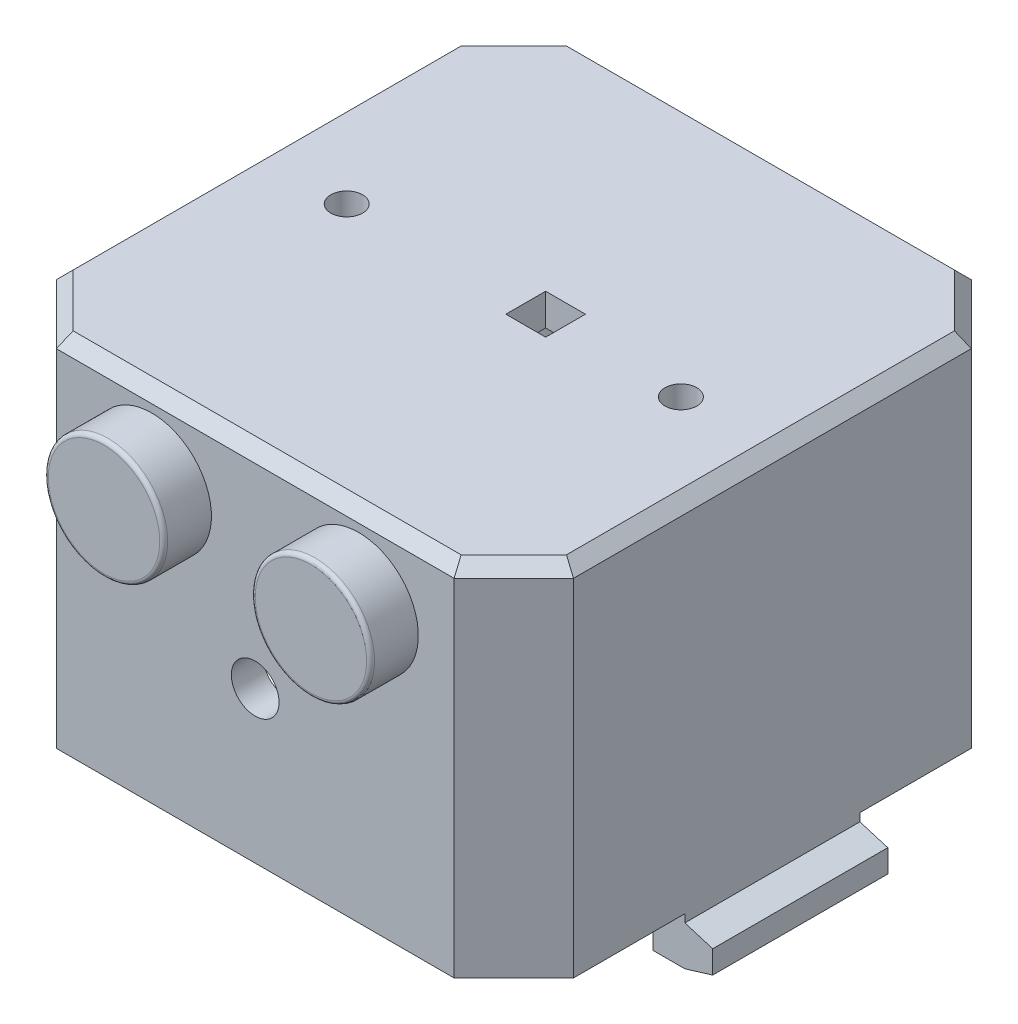
SolidWorks part; units mm, degrees
ref_plane "Alzado" through (0, 0, 0) normal (0, 0, 1) x (1, 0, 0)
ref_plane "Planta" through (0, 0, 0) normal (0, 1, 0) x (1, 0, 0)
ref_plane "Vista lateral" through (0, 0, 0) normal (1, 0, 0) x (0, 0, -1)
sketch "Croquis1" plane through (0, 0, 0) normal (0, 1, 0) x (1, 0, 0)
  line L1 (-25, -32.5) -> (25, -32.5)
  line L3 (-25, 32.5) -> (25, 32.5)
  line L5 (-25, -32.5) -> (25, 32.5) construction
  line L6 (-25, 32.5) -> (25, -32.5) construction
  line L10 (32.5, 25) -> (32.5, -25)
  line L11 (25, -32.5) -> (32.5, -25)
  line L12 (32.5, 25) -> (25, 32.5)
  line L13 (-32.5, 25) -> (-32.5, -25)
  line L14 (-32.5, -25) -> (-25, -32.5)
  line L15 (-32.5, 25) -> (-25, 32.5)
  point P0 (0, 0)
  point P10 (0, 32.5)
  dimension "D1" = 65
  dimension "D2" = 65
  dimension "D3" = 50
  dimension "D4" = 50
  dimension "D5" = 25
  dimension "D6" = 25
extrude "Saliente-Extruir1" add sketch "Croquis1" along normal blind 45
shell "Vaciado2" thickness 4 removed face at (0, 0, 0)
chamfer "Chaflán3" distance 1.5 angle 45 8 edges at (0, 45, -32.5) (32.5, 45, 0) (0, 45, 32.5) (-32.5, 45, 0) (-28.75, 45, 28.75) (28.75, 45, 28.75) (28.75, 45, -28.75) (-28.75, 45, -28.75)
sketch "Croquis2" plane through (0, 0, 32.5) normal (0, 0, 1) x (1, 0, 0)
  line L0 (0, 0) -> (0, 6.916) construction
  circle A0 centre (13, 35) radius 7.5
  circle A1 centre (-13, 35) radius 7.5
  dimension "D1" = 15
  dimension "D2" = 13
  dimension "D3" = 35
extrude "Saliente-Extruir2" add sketch "Croquis2" along normal blind 6
sketch "Croquis4" plane through (0, 0, 28.5) normal (0, 0, -1) x (-1, 0, 0)
  line L0 (0, 0) -> (0, 4.7403) construction
  line L1 (0, 0) -> (0, 6.916) construction
  circle A0 centre (-13, 35) radius 5
  circle A1 centre (13, 35) radius 5
  dimension "D1" = 10
extrude "Cortar-Extruir2" cut sketch "Croquis4" against normal blind 8
fillet "Redondeo1" radius 0.5 2 edges at (-20.5, 35, 38.5) (20.5, 35, 38.5)
sketch "Croquis5" plane through (0, 0, 32.5) normal (0, 0, 1) x (1, 0, 0)
  circle A0 centre (0, 19) radius 3
  dimension "D2" = 6
  dimension "D1" = 19
extrude "Cortar-Extruir3" cut sketch "Croquis5" against normal blind 10
sketch "Croquis13" plane through (0, 0, 36.5) normal (0, 0, -1) x (-1, 0, 0)
  circle A0 centre (-13, 35) radius 2.6
  circle A1 centre (13, 35) radius 2.6
  circle A2 centre (13, 35) radius 5
  circle A3 centre (-13, 35) radius 5
  dimension "D1" = 5.2
  dimension "D2" = 5.2
extrude "Saliente-Extruir8" add sketch "Croquis13" along normal blind 8
sketch "Croquis7" plane through (0, 0, 28.5) normal (0, 0, -1) x (-1, 0, 0)
  line L0 (23.3431, 0) -> (-23.3431, 0) construction
  line L1 (-14.08, 8) -> (-9.08, 8)
  line L2 (-14.08, 8) -> (-14.08, 13)
  line L3 (-14.08, 13) -> (-9.08, 13)
  line L4 (-9.08, 8) -> (-9.08, 13)
  line L5 (-14.08, 8) -> (-9.08, 13) construction
  line L6 (-14.08, 13) -> (-9.08, 8) construction
  line L8 (-14.08, 25.5) -> (-9.08, 25.5)
  line L9 (-14.08, 25.5) -> (-14.08, 30.5)
  line L10 (-14.08, 30.5) -> (-9.08, 30.5)
  line L11 (-9.08, 25.5) -> (-9.08, 30.5)
  line L12 (-14.08, 25.5) -> (-9.08, 30.5) construction
  line L13 (-14.08, 30.5) -> (-9.08, 25.5) construction
  line L14 (13.93, 13) -> (8.93, 8) construction
  line L15 (13.93, 8) -> (8.93, 13) construction
  line L16 (8.93, 8) -> (8.93, 13)
  line L17 (13.93, 13) -> (8.93, 13)
  line L18 (13.93, 8) -> (13.93, 13)
  line L19 (13.93, 8) -> (8.93, 8)
  line L20 (13.93, 30.5) -> (8.93, 25.5) construction
  line L21 (13.93, 25.5) -> (8.93, 30.5) construction
  line L22 (8.93, 25.5) -> (8.93, 30.5)
  line L23 (13.93, 30.5) -> (8.93, 30.5)
  line L24 (13.93, 25.5) -> (13.93, 30.5)
  line L25 (13.93, 25.5) -> (8.93, 25.5)
  point P0 (-11.58, 10.5)
  point P8 (-11.58, 28)
  point P13 (0, 0)
  point P15 (11.43, 10.5)
  point P16 (11.43, 28)
  point P20 (11.43, 10.5)
  point P25 (11.43, 28)
  point P26 (-11.58, 28)
  point P27 (11.43, 28)
  point P28 (11.43, 10.5)
  point P29 (-11.58, 10.5)
  dimension "D1" = 10.5
  dimension "D2" = 5
  dimension "D3" = 5
  dimension "D4" = 11.58
  dimension "D5" = 5
  dimension "D6" = 5
  dimension "D7" = 28
  dimension "D8" = 23.01
  dimension "D9" = 23.01
  dimension "D10" = 5
  dimension "D11" = 5
  dimension "D12" = 5
  dimension "D13" = 5
  dimension "D14" = 10.5
  dimension "D15" = 28
extrude "Saliente-Extruir3" add sketch "Croquis7" along normal blind 1
sketch "Croquis8" plane through (0, 0, 27.5) normal (0, 0, -1) x (-1, 0, 0)
  line L0 (0, 0) -> (0, 4.8013) construction
  line L1 (23.3431, 0) -> (-23.3431, 0) construction
  circle A0 centre (-11.505, 10.4893) radius 2.5
  circle A1 centre (-11.505, 27.9763) radius 2.5
  circle A2 centre (11.505, 10.4893) radius 2.5
  circle A3 centre (11.505, 27.9763) radius 2.5
  dimension "D1" = 5
  dimension "D2" = 5
  dimension "D5" = 5
  dimension "D3" = 23.01
  dimension "D4" = 23.01
extrude "Saliente-Extruir4" add sketch "Croquis8" along normal blind 1
sketch "Croquis9" plane through (0, 0, 26.5) normal (0, 0, -1) x (-1, 0, 0)
  circle A0 centre (-11.505, 27.9763) radius 1.6
  circle A1 centre (-11.505, 10.4893) radius 1.6
  circle A2 centre (11.505, 10.4893) radius 1.6
  circle A3 centre (11.505, 27.9763) radius 1.6
  dimension "D1" = 3.2
  dimension "D2" = 3.2
  dimension "D3" = 3.2
  dimension "D4" = 3.2
extrude "Cortar-Extruir5" cut sketch "Croquis9" against normal blind 4
sketch "Croquis12" plane through (0, 41, 0) normal (0, -1, 0) x (1, 0, 0)
  line L0 (0, 0) -> (-5.199, 0) construction
  line L1 (-21.9, -8.93) -> (21.9, -8.93) construction
  line L2 (-21.9, -8.93) -> (-21.9, 8.93) construction
  line L3 (-21.9, 8.93) -> (21.9, 8.93) construction
  line L4 (21.9, -8.93) -> (21.9, 8.93) construction
  line L5 (-21.9, -8.93) -> (21.9, 8.93) construction
  line L6 (-21.9, 8.93) -> (21.9, -8.93) construction
  line L7 (0, 0) -> (0, 4.1573) construction
  circle A0 centre (-20.65, 7.68) radius 0.8
  circle A1 centre (-20.65, 7.68) radius 1.15
  circle A2 centre (-20.65, -7.68) radius 1.15
  circle A3 centre (-20.65, -7.68) radius 0.8
  circle A4 centre (20.65, 7.68) radius 1.15
  circle A5 centre (20.65, 7.68) radius 0.8
  circle A6 centre (20.65, -7.68) radius 1.15
  circle A7 centre (20.65, -7.68) radius 0.8
  point P0 (0, 0)
  dimension "D6" = 1.6
  dimension "D4" = 2.3
  dimension "D1" = 43.8
  dimension "D2" = 17.86
  dimension "D3" = 1.25
  dimension "D7" = 1.25
extrude "Saliente-Extruir7" add sketch "Croquis12" along normal blind 6
sketch "Croquis14" plane through (0, 41, 0) normal (0, -1, 0) x (1, 0, 0)
  line L1 (-22.15, 6.43) -> (-19.15, 6.43)
  line L2 (-22.15, 6.43) -> (-22.15, 8.93)
  line L3 (-22.15, 8.93) -> (-19.15, 8.93)
  line L4 (-19.15, 6.43) -> (-19.15, 8.93)
  line L5 (-22.15, 6.43) -> (-19.15, 8.93) construction
  line L6 (-22.15, 8.93) -> (-19.15, 6.43) construction
  line L7 (-22.15, -8.93) -> (-19.15, -8.93)
  line L8 (-22.15, -8.93) -> (-22.15, -6.43)
  line L9 (-22.15, -6.43) -> (-19.15, -6.43)
  line L10 (-19.15, -8.93) -> (-19.15, -6.43)
  line L11 (-22.15, -8.93) -> (-19.15, -6.43) construction
  line L12 (-22.15, -6.43) -> (-19.15, -8.93) construction
  line L13 (19.15, 6.43) -> (22.15, 6.43)
  line L14 (19.15, 6.43) -> (19.15, 8.93)
  line L15 (19.15, 8.93) -> (22.15, 8.93)
  line L16 (22.15, 6.43) -> (22.15, 8.93)
  line L17 (19.15, 6.43) -> (22.15, 8.93) construction
  line L18 (19.15, 8.93) -> (22.15, 6.43) construction
  line L19 (19.15, -8.93) -> (22.15, -8.93)
  line L20 (19.15, -8.93) -> (19.15, -6.43)
  line L21 (19.15, -6.43) -> (22.15, -6.43)
  line L22 (22.15, -8.93) -> (22.15, -6.43)
  line L23 (19.15, -8.93) -> (22.15, -6.43) construction
  line L24 (19.15, -6.43) -> (22.15, -8.93) construction
  point P0 (-20.65, 7.68)
  point P6 (-20.65, -7.68)
  point P12 (20.65, 7.68)
  point P18 (20.65, -7.68)
  dimension "D1" = 3
  dimension "D2" = 2.5
  dimension "D3" = 3
  dimension "D4" = 2.5
  dimension "D5" = 3
  dimension "D6" = 2.5
  dimension "D7" = 3
  dimension "D8" = 2.5
extrude "Saliente-Extruir9" add sketch "Croquis14" along normal blind 5
sketch "Croquis15" plane through (-32.5, 0, 0) normal (-1, 0, 0) x (0, 0, 1)
  line L1 (-6, 40.5) -> (6, 40.5)
  line L2 (-6, 40.5) -> (-6, 32.5)
  line L3 (-6, 32.5) -> (6, 32.5)
  line L4 (6, 40.5) -> (6, 32.5)
  dimension "D1" = 8
  dimension "D2" = 12
  dimension "D3" = 3
  dimension "D4" = 19
extrude "Cortar-Extruir6" cut sketch "Croquis15" against normal blind 7
sketch "Croquis16" plane through (0, 0, -28.5) normal (0, 0, 1) x (1, 0, 0)
  line L2 (18.95, 6.05) -> (6.55, 6.05)
  line L3 (18.95, 6.05) -> (18.95, 18.45)
  line L4 (18.95, 18.45) -> (6.55, 18.45)
  line L5 (6.55, 6.05) -> (6.55, 18.45)
  line L6 (5.5, 5) -> (20, 5)
  line L7 (5.5, 5) -> (5.5, 19.5)
  line L8 (5.5, 19.5) -> (20, 19.5)
  line L9 (20, 5) -> (20, 19.5)
  line L10 (5.5, 5) -> (20, 19.5) construction
  line L11 (5.5, 19.5) -> (20, 5) construction
  line L12 (18.95, 6.05) -> (6.55, 18.45) construction
  line L13 (18.95, 18.45) -> (6.55, 6.05) construction
  point P0 (12.75, 12.25)
  point P4 (12.75, 12.25)
  dimension "D1" = 12.4
  dimension "D2" = 12.4
  dimension "D3" = 5
  dimension "D4" = 5
  dimension "D5" = 14.5
  dimension "D6" = 14.5
extrude "Saliente-Extruir10" add sketch "Croquis16" along normal blind 3
sketch "Croquis17" plane through (0, 0, -28.5) normal (0, 0, 1) x (1, 0, 0)
  circle A0 centre (12.75, 12.25) radius 5.5
  point P4 (12.75, 12.25)
  dimension "D1" = 11
extrude "Cortar-Extruir7" cut sketch "Croquis17" against normal through all
sketch "Croquis18" plane through (0, 0, 0) normal (0, -1, 0) x (1, 0, 0)
  line L1 (-32.5, 11) -> (-28.5, 11)
  line L2 (-32.5, 11) -> (-32.5, -11)
  line L3 (-32.5, -11) -> (-28.5, -11)
  line L4 (-28.5, 11) -> (-28.5, -11)
  line L5 (-32.5, -25) -> (-32.5, 25) construction
  line L6 (0, 0) -> (0, 8.739) construction
  line L7 (28.5, 11) -> (28.5, -11)
  line L8 (32.5, -11) -> (28.5, -11)
  line L9 (32.5, 11) -> (32.5, -11)
  line L10 (32.5, 11) -> (28.5, 11)
  point P4 (-28.5, 0)
  dimension "D1" = 4
  dimension "D2" = 22
extrude "Saliente-Extruir11" add sketch "Croquis18" along normal blind 6
sketch "Croquis19" plane through (0, 0, 11) normal (0, 0, 1) x (1, 0, 0)
  line L0 (-32.5, -3.5) -> (-34.5, -3.5) construction
  line L1 (36, -2.0667) -> (36, -4.9333)
  line L2 (-34.5, -2.0568) -> (-32.5, -1)
  line L3 (-32.5, -6) -> (-32.5, 0)
  line L4 (-32.5, -6) -> (-32.5, -1)
  line L5 (-32.5, -6) -> (-34.5, -4.9432)
  line L6 (0, 0) -> (0, 6.3616) construction
  line L7 (-25, 0) -> (25, 0) construction
  line L8 (32.5, -3.5) -> (36, -3.5) construction
  line L9 (32.5, -6) -> (36, -4.9333)
  line L10 (32.5, -6) -> (32.5, -1)
  line L11 (32.5, -6) -> (32.5, 0)
  line L12 (36, -2.0667) -> (32.5, -1)
  line L14 (-34.5, -2.0568) -> (-34.5, -4.9432)
  line M6 (-32.5, 0) -> (-32.5, -6)
  dimension "D1" = 2
  dimension "D2" = 3.5
extrude "Saliente-Extruir13" add sketch "Croquis19" against normal blind 22 contours L5 L2 M6 | L12 L10 L9 region at (34.0918, -3.5, 11) region at (-33.4107, -3.5, 11)
sketch "Croquis20" plane through (0, 45, 0) normal (0, 1, 0) x (1, 0, 0)
  line L1 (6.0029, -2) -> (1.0029, -2)
  line L2 (6.0029, -2) -> (6.0029, 3)
  line L3 (6.0029, 3) -> (1.0029, 3)
  line L4 (1.0029, -2) -> (1.0029, 3)
  dimension "D1" = 5
  dimension "D2" = 5
  dimension "D3" = 2
extrude "Cortar-Extruir8" cut sketch "Croquis20" against normal blind 10
sketch "Croquis10" plane through (0, 45, 0) normal (0, 1, 0) x (1, 0, 0)
  line L0 (-31, 24.3787) -> (-31, -24.3787) construction
  line L1 (-31, -4) -> (-11, -4) construction
  line L2 (-31, -4) -> (-31, 4) construction
  line L3 (-31, 4) -> (-11, 4) construction
  line L4 (-11, -4) -> (-11, 4) construction
  line L5 (-31, -4) -> (-11, 4) construction
  line L6 (-31, 4) -> (-11, -4) construction
  line L7 (0, 0) -> (0, 7.307) construction
  line L8 (31, 4) -> (11, -4) construction
  line L9 (31, -4) -> (11, 4) construction
  line L10 (11, -4) -> (11, 4) construction
  line L11 (31, 4) -> (11, 4) construction
  line L12 (31, -4) -> (31, 4) construction
  line L13 (31, -4) -> (11, -4) construction
  circle A0 centre (-21, 0) radius 2
  circle A1 centre (21, 0) radius 2
  point P0 (-21, 0)
  point P14 (21, 0)
  dimension "D3" = 4
  dimension "D4" = 4
  dimension "D1" = 20
  dimension "D2" = 8
extrude "Cortar-Extruir10" cut sketch "Croquis10" against normal through all
sketch "Croquis21" plane through (0, 36, 0) normal (0, -1, 0) x (1, 0, 0)
  circle A0 centre (-20.65, 7.68) radius 0.8
  circle A1 centre (20.65, 7.68) radius 0.8
  circle A2 centre (20.65, -7.68) radius 0.8
  circle A3 centre (-20.65, -7.68) radius 0.8
extrude "Cortar-Extruir11" cut sketch "Croquis21" against normal blind 5
